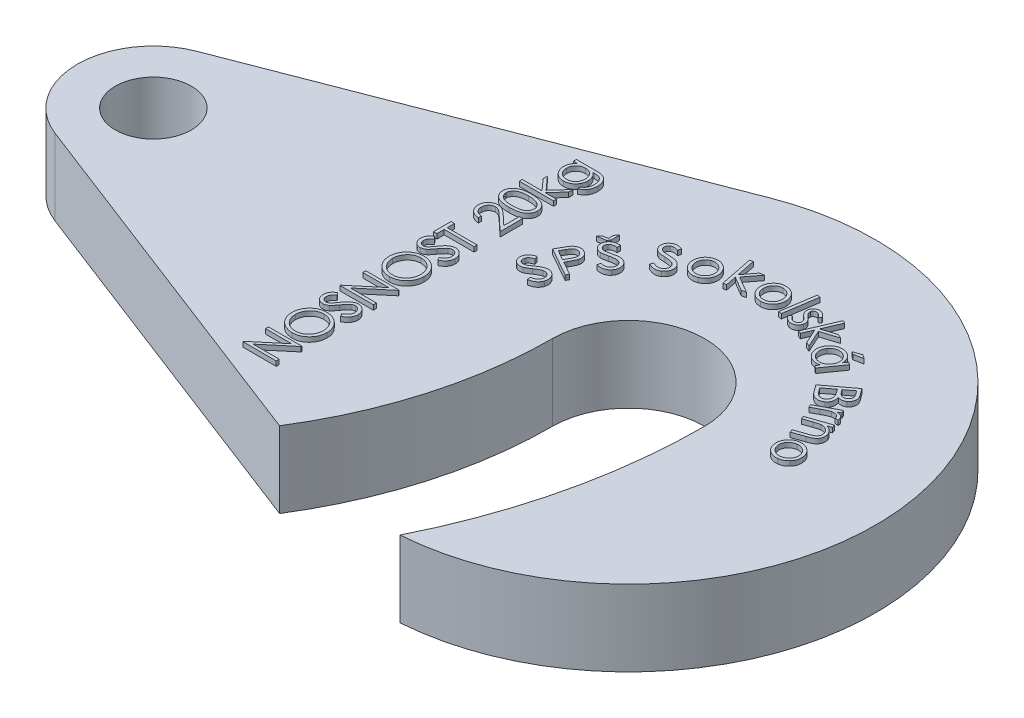
SolidWorks part; units mm, degrees
ref_plane "Front Plane" through (0, 0, 0) normal (0, 0, 1) x (1, 0, 0)
ref_plane "Top Plane" through (0, 0, 0) normal (0, 1, 0) x (1, 0, 0)
ref_plane "Right Plane" through (0, 0, 0) normal (1, 0, 0) x (0, 0, -1)
sketch "Sketch1" plane through (0, 0, 0) normal (0, 1, 0) x (1, 0, 0)
  line L0 (0, 0) -> (19216.6997, 0) construction
  line L1 (-2.88, 7.4636) -> (40.64, 24.2568)
  line L2 (-2.88, -7.4636) -> (35.5866, -22.3068)
  circle A0 centre (0, 0) radius 4
  arc A1 (-2.88, 7.4636) -> (-2.88, -7.4636) centre (0, 0) ccw
  arc A2 (50, 0) -> (30, -40) centre (0, 0) cw construction
  arc A3 (51.88, -25.9319) -> (58, 0) centre (0, 0) ccw
  arc A4 (35.5866, -22.3068) -> (42, 0) centre (0, 0) ccw
  arc A6 (58, 0) -> (42, 0) centre (50, 0) ccw
  arc A7 (51.88, -25.9319) -> (40.64, 24.2568) centre (50, 0) ccw
  point P5 (31.2208, -39.0546)
  dimension "D1" = 8
  dimension "D2" = 16
  dimension "D3" = 8
  dimension "D4" = 50
  dimension "D5" = 52
  dimension "D8" = 40
extrude "Boss-Extrude1" add sketch "Sketch1" along normal blind 8
sketch "Sketch2" plane through (0, 8, 0) normal (0, 1, 0) x (1, 0, 0)
  line L0 (30, 20) -> (30, -20) construction
  line L1 (0, 0) -> (50, 0) construction
  arc A0 (36, 0) -> (64, 0) centre (50, 0) cw construction
  circle A1 centre (0, 0) radius 4 construction
  text T0 "SPŠ Sokolská Brno"
  text T1 "NOSNOST 20kg" font "Century Gothic" height 3.5
  point P8 (30, 0)
  point P12 (64.1432, 3.5191)
  point P13 (0, 0)
  point P14 (0, 0)
  dimension "D1" = 30
  dimension "D3" = 14
  dimension "D2" = 40
extrude "Boss-Extrude2" add sketch "Sketch2" along normal blind 0.5
